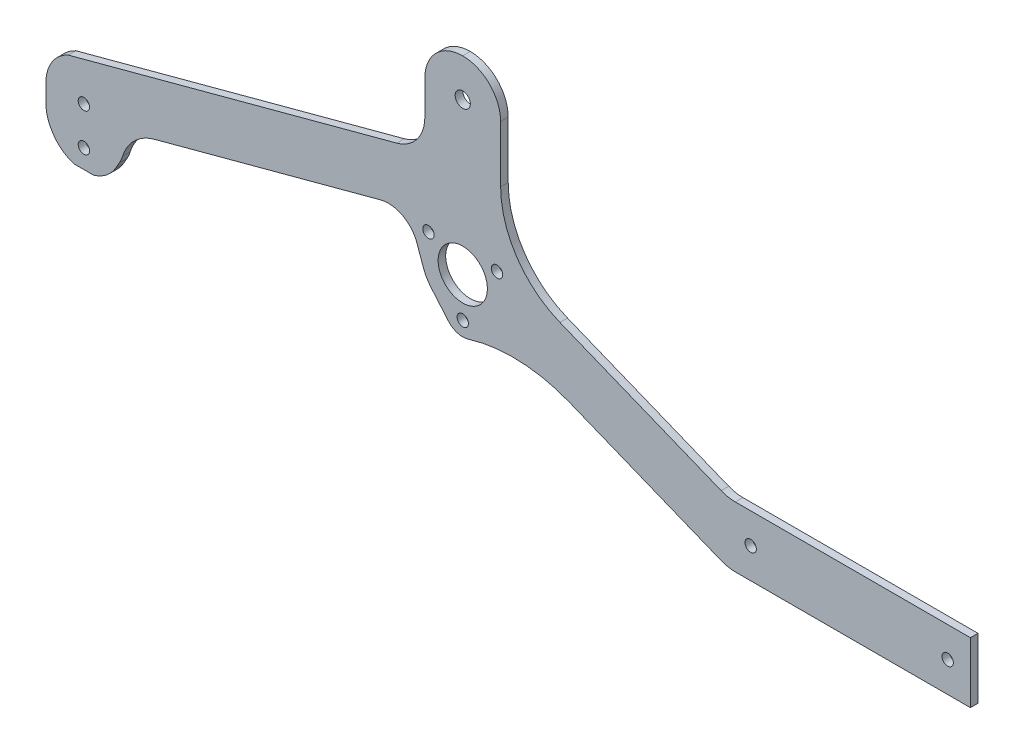
SolidWorks part; units mm, degrees
ref_plane "Спереди" through (0, 0, 0) normal (0, 0, 1) x (1, 0, 0)
ref_plane "Сверху" through (0, 0, 0) normal (0, 1, 0) x (1, 0, 0)
ref_plane "Справа" through (0, 0, 0) normal (1, 0, 0) x (0, 0, -1)
sketch "эскиз" plane through (0, 0, 0) normal (0, 0, 1) x (1, 0, 0)
  line L0 (110, -110) -> (110, -24) construction
  line L1 (-30, -110) -> (-30, -24) construction
  line L2 (-170, -24) -> (-136, -24) construction
  line L3 (-170, -110) -> (-30, -110) construction
  line L4 (-170, -24) -> (-188, -24) construction
  line L5 (-30, -110) -> (110, -110) construction
  line L6 (-170, -110) -> (-170, -24) construction
  line L7 (76, -24) -> (110, -24) construction
  line L8 (128, -24) -> (110, -24) construction
  line L9 (-42.5, -24) -> (-17.5, -24) construction
  line L10 (-170, -24) -> (-100, -24) construction
  line L11 (-100, -24) -> (-30, -24) construction
  line L12 (-100, -24) -> (0, 0) construction
  line L13 (0, 0) -> (110, -24) construction
  line L14 (-100, -24) -> (-100, -11) construction
  circle A0 centre (-170, -110) radius 57.5 construction
  circle A1 centre (-30, -110) radius 57.5 construction
  circle A2 centre (110, -110) radius 57.5 construction
  circle A3 centre (-188, -24) radius 1.5 construction
  circle A4 centre (-136, -24) radius 1.5 construction
  circle A5 centre (76, -24) radius 1.5 construction
  circle A6 centre (128, -24) radius 1.5 construction
  circle A7 centre (-42.5, -24) radius 1.5 construction
  circle A8 centre (-17.5, -24) radius 1.5 construction
  circle A9 centre (-100, -11) radius 1.5
  circle A10 centre (-100, -21) radius 1.5
  circle A11 centre (-100, -36) radius 2
  circle A12 centre (0, 40) radius 2
  point P31 (-153, -24)
  dimension "D1" = 115
  dimension "D4" = 3
  dimension "D7" = 25
  dimension "D12" = 3
  dimension "D11" = 4
  dimension "D17" = 4
  dimension "D2" = 140
  dimension "D3" = 86
  dimension "D5" = 18
  dimension "D6" = 34
  dimension "D8" = 70
  dimension "D9" = 280
  dimension "D10" = 30
  dimension "D13" = 10
  dimension "D14" = 12
  dimension "D15" = 110
  dimension "D16" = 15
  dimension "D18" = 40
sketch "эскиз 1" plane through (0, 0, 0) normal (0, 0, 1) x (1, 0, 0)
  line L0 (-194, -16) -> (-194, -32)
  line L1 (-194, -32) -> (-124, -32)
  line L2 (-124, -32) -> (-124, -47)
  line L3 (-194, -16) -> (-120, -16)
  line L5 (-11, -32) -> (-11, -16)
  line L6 (-124, -47) -> (-76, -47)
  line L9 (-109, -27) -> (-91, -27)
  line L10 (-76, -32) -> (-76, -47)
  line L11 (-30, -16) -> (-30, -42) construction
  line L12 (-76, -32) -> (-11, -32)
  line L13 (-11, -32) -> (-76, -32)
  line L15 (-80, -16) -> (-11, -16)
  line L16 (-100, -24) -> (-100, -11) construction
  line L17 (-30, -110) -> (-30, -24) construction
  line L18 (-170, -16) -> (-170, -32) construction
  line L19 (-170, -110) -> (-170, -24) construction
  line L20 (-170, -24) -> (-188, -24) construction
  line L21 (-100, -27) -> (-100, -47) construction
  line L22 (-109, -27) -> (-120, -16)
  line L23 (-91, -27) -> (-80, -16)
  circle A0 centre (-188, -24) radius 1.5
  circle A1 centre (-136, -24) radius 1.5
  circle A2 centre (-100, -36) radius 2
  circle A3 centre (-42.5, -24) radius 1.5
  circle A4 centre (-17.5, -24) radius 1.5
  circle A5 centre (-17.5, -24) radius 1.5 construction
  circle A6 centre (-42.5, -24) radius 1.5 construction
  circle A7 centre (-100, -36) radius 2 construction
  circle A8 centre (-136, -24) radius 1.5 construction
  circle A9 centre (-188, -24) radius 1.5 construction
  point P11 (-100, -27)
  point P25 (-100, -47)
  dimension "D1" = 24
  dimension "D2" = 19
  dimension "D3" = 16
  dimension "D4" = 11
  dimension "D5" = 45
  dimension "D7" = 70
  dimension "D8" = 8
  dimension "D9" = 3
extrude "тело маленькой арки" [suppressed] add sketch "эскиз 1" along normal blind 2
chamfer "Фаска1" [suppressed] distance 11 angle 45
sketch "Эскиз1" plane through (0, 0, 0) normal (0, 0, 1) x (1, 0, 0)
  line L0 (10, 8.208) -> (70, -16)
  line L1 (70, -16) -> (134, -16)
  line L2 (134, -16) -> (134, -32)
  line L3 (134, -32) -> (70, -32)
  line L4 (70, -32) -> (8.372, -7.1351)
  line L5 (-100, -24) -> (-30, -24) construction
  line L6 (-12.7222, 2.951) -> (-14.5644, 8.1359)
  line L7 (10, 8.208) -> (10, 50)
  line L8 (-104.0983, -1.8784) -> (-10, 23.3352)
  line L9 (76, -24) -> (110, -24) construction
  line L10 (-12.7222, 2.951) -> (-10.3652, -3.6828)
  line L11 (-90, -12.077) -> (-14.5644, 8.1359)
  line L12 (-8.9167, 9.5422) -> (-1.9932, 10.8179) construction
  line L13 (110, -110) -> (110, -24) construction
  line L14 (3.8054, -12.4932) -> (8.372, -7.1351)
  line L15 (-3.8054, -12.4932) -> (-8.372, -7.1351)
  line L16 (-110, -26) -> (-90, -26)
  line L18 (-100, -11) -> (-100, -26) construction
  line L19 (-100, -24) -> (-100, -11) construction
  line L20 (8.9167, 9.5422) -> (1.9932, 10.8179) construction
  line L21 (-90, -26) -> (-90, -12.077)
  line L22 (10, 50) -> (-10, 50)
  line L24 (-10, 50) -> (-10, 23.3352)
  line L27 (12.7222, 2.951) -> (10.3652, -3.6828) construction
  line L31 (-110, -11) -> (-110, -26)
  circle A0 centre (-100, -21) radius 1.5
  circle A1 centre (-100, -11) radius 1.5
  circle A2 centre (-100, -11) radius 1.5 construction
  circle A3 centre (-100, -21) radius 1.5 construction
  circle A4 centre (0, 0) radius 6.5
  circle A5 centre (0, 0) radius 11 construction
  arc A6 (-8.9167, 9.5422) -> (-12.7222, 2.951) centre (-8.0107, 4.625) ccw construction
  arc A7 (1.9932, 10.8179) -> (-1.9932, 10.8179) centre (0, 0) ccw construction
  arc A8 (-3.8054, -12.4932) -> (3.8054, -12.4932) centre (0, -9.25) ccw
  arc A9 (12.7222, 2.951) -> (8.9167, 9.5422) centre (8.0107, 4.625) ccw construction
  arc A10 (8.372, -7.1351) -> (10.3652, -3.6828) centre (0, 0) ccw construction
  arc A11 (-10.3652, -3.6828) -> (-8.372, -7.1351) centre (0, 0) ccw
  circle A12 centre (0, 0) radius 9.25 construction
  circle A13 centre (0, -10.45) radius 1.5
  circle A14 centre (-9.05, 5.225) radius 1.5
  circle A15 centre (9.05, 5.225) radius 1.5
  circle A16 centre (0, 0) radius 7.65 construction
  circle A17 centre (128, -24) radius 1.5
  circle A18 centre (76, -24) radius 1.5
  circle A19 centre (76, -24) radius 1.5 construction
  circle A20 centre (128, -24) radius 1.5 construction
  circle A21 centre (0, 40) radius 2
  circle A22 centre (0, 40) radius 2 construction
  arc A24 (-104.0983, -1.8784) -> (-110, -11) centre (-100, -11) ccw
  point P0 (-87.4368, -12.4932)
  point P6 (26.311, 3.5068)
  point P27 (134, -24)
  point P33 (0, 50)
  point P62 (0, 0)
  point P68 (0, 0)
  point P79 (10.3652, -9.25)
  point P80 (0, 0)
  point P81 (8.9167, -7.1351)
  dimension "D2" = 13
  dimension "D3" = 3
  dimension "D5" = 5
  dimension "D6" = 18.5
  dimension "D7" = 22
  dimension "D14" = 3
  dimension "D17" = 15.3
  dimension "D20" = 20
  dimension "D13" = 13.5
  dimension "D4" = 15
  dimension "D1" = 16
  dimension "D8" = 10
  dimension "D9" = 6
  dimension "D10" = 24
  dimension "D12" = 74
  dimension "D15" = 3
  dimension "D19" = 10.45
  dimension "D21" = 5
extrude "тело большой арки" add sketch "Эскиз1" along normal blind 2
sketch "Эскиз2" plane through (0, 0, 2) normal (0, 0, 1) x (1, 0, 0)
  line L0 (-110, -18.6795) -> (-106.364, -24.9773)
  line L3 (-106.364, -24.9773) -> (-102.5472, -26)
  line L6 (-100, -36) -> (-100, -7.7157) construction
  line L12 (-110, -18.6795) -> (-110, -26)
  line L13 (-110, -11) -> (-110, -26) construction
  line L14 (-110, -26) -> (-90, -26) construction
  line L15 (-110, -26) -> (-102.5472, -26)
  line L19 (-90, -26) -> (-97.4528, -26)
  line L20 (-90, -18.6795) -> (-90, -26)
  line L21 (-93.636, -24.9773) -> (-97.4528, -26)
  line L22 (-90, -18.6795) -> (-93.636, -24.9773)
  line L23 (-100, -24) -> (-30, -24) construction
  circle A2 centre (-100, -36) radius 28.2843 construction
  circle A3 centre (-100, -36) radius 12.7279 construction
  dimension "D1" = 60
  dimension "D2" = 135
extrude "Упоры" cut sketch "Эскиз2" against normal up to next
fillet "Скругление5" radius 10 2 edges at (-106.364, -24.9773, 1) (-93.636, -24.9773, 1)
fillet "Скругление1" [suppressed] radius 10
fillet "Скругление2" [suppressed] radius 10
fillet "Скругление3" [suppressed] radius 15
fillet "Скругление4" [suppressed] radius 15
fillet "Скругление6" radius 12 1 edges at (-90, -12.077, 1)
fillet "Скругление7" radius 8 1 edges at (-14.5644, 8.1359, 1)
fillet "Скругление8" radius 40 1 edges at (8.372, -7.1351, 1)
fillet "Скругление9" radius 10 3 edges at (-10, 23.3352, 1) (10, 50, 1) (-10, 50, 1)
fillet "Скругление10" radius 25 1 edges at (10, 8.208, 1)
fillet "Скругление11" radius 10 4 edges at (-90, -18.6795, 1) (-110, -18.6795, 1) (70, -32, 1) (70, -16, 1)
